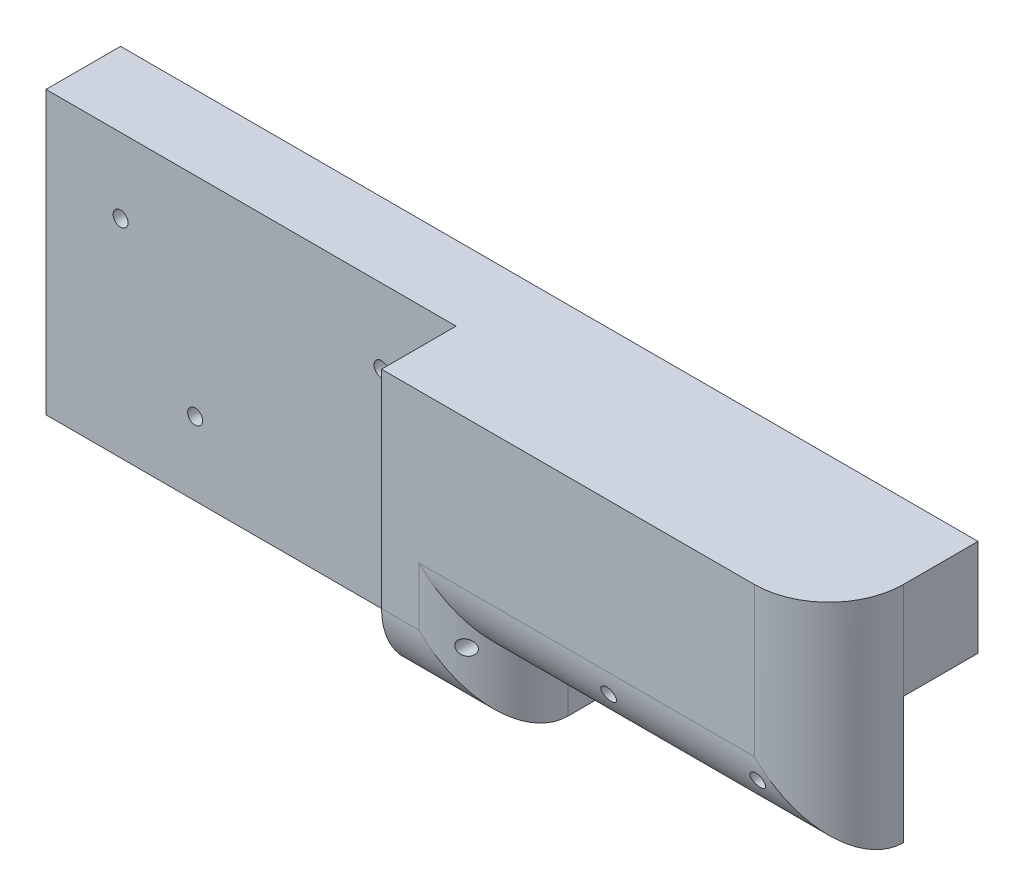
SolidWorks part; units mm, degrees
ref_plane "Plan de face" through (0, 0, 0) normal (0, 0, 1) x (1, 0, 0)
ref_plane "Plan de dessus" through (0, 0, 0) normal (0, 1, 0) x (1, 0, 0)
ref_plane "Plan de droite" through (0, 0, 0) normal (1, 0, 0) x (0, 0, -1)
sketch "Esquisse1" plane through (0, 0, 40) normal (0, 0, 1) x (1, 0, 0)
  line L0 (-121.1414, -130.4642) -> (-181.1414, -130.4642)
  line L1 (-121.1414, -130.4642) -> (-121.1414, -100.4642)
  line L2 (-181.1414, -130.4642) -> (-181.1414, -100.4642)
  line L3 (-121.1414, -100.4642) -> (-181.1414, -100.4642)
  line L6 (-181.1414, -130.4642) -> (-181.1414, -138.2665)
  line L7 (-181.1414, -130.4642) -> (-166.1414, -130.4642)
  line L8 (-181.1414, -138.2665) -> (-166.1414, -138.2665)
  line L9 (-166.1414, -130.4642) -> (-166.1414, -138.2665)
  line L12 (-166.1414, 57.3381) -> (-166.1414, 49.5358) construction
  line L13 (-181.1414, 57.3381) -> (-181.1414, 19.5358) construction
  line M11 (-166.1414, -125.4642) -> (-166.1414, -130.4642)
  line M14 (-121.1414, -113.4642) -> (-161.1414, -113.4642)
  line M15 (-161.1414, -113.4642) -> (-161.1414, -125.4642)
  line M16 (-161.1414, -125.4642) -> (-166.1414, -125.4642)
  dimension "D2" = 30
extrude "Boss.-Extru.1" add sketch "Esquisse1" along normal blind 10 contours L1 L3 L2 L0 M11 M16 M15 M14 | L9 L0 L6 L8 | L0 L1 L3 L2 region at (-173.6414, -134.3653, 40) region at (-157.0661, -111.1423, 40)
sketch "Esquisse2" plane through (0, 0, 40) normal (0, 0, -1) x (-1, 0, 0)
  line L0 (121.1414, -100.4642) -> (121.1414, -113.4642)
  line L1 (121.1414, -100.4642) -> (161.1414, -100.4642)
  line L2 (121.1414, -113.4642) -> (161.1414, -113.4642)
  line L3 (161.1414, -100.4642) -> (161.1414, -113.4642)
  line L4 (121.1414, -130.4642) -> (121.1414, -100.4642) construction
  line L5 (161.1414, -113.4642) -> (121.1414, -113.4642) construction
  line L6 (181.1414, -138.2665) -> (181.1414, -100.4642) construction
  line L7 (161.1414, -100.4642) -> (161.1414, -125.4642)
  line L8 (161.1414, -100.4642) -> (181.1414, -100.4642)
  line L9 (161.1414, -125.4642) -> (181.1414, -125.4642)
  line L10 (181.1414, -100.4642) -> (181.1414, -125.4642)
  line L11 (181.1414, -138.2665) -> (166.1414, -138.2665) construction
  line L12 (166.1414, -138.2665) -> (166.1414, -125.4642)
  line L13 (166.1414, -138.2665) -> (236.1414, -138.2665)
  line L14 (166.1414, -125.4642) -> (236.1414, -125.4642)
  line L15 (236.1414, -138.2665) -> (236.1414, -125.4642)
  line L17 (236.1414, 19.5358) -> (236.1414, 57.3381) construction
  line L18 (181.1414, -125.4642) -> (181.1414, -100.4642)
  line L19 (181.1414, -125.4642) -> (236.1414, -125.4642)
  line L20 (181.1414, -100.4642) -> (236.1414, -100.4642)
  line L21 (236.1414, -125.4642) -> (236.1414, -100.4642)
  point P9 (171.1414, -100.4642)
  point P18 (166.1414, -138.2665)
  line M7 (166.1414, -130.4642) -> (166.1414, -138.2665)
  line M8 (166.1414, -138.2665) -> (181.1414, -138.2665)
  line M9 (181.1414, -138.2665) -> (181.1414, -100.4642)
  line M10 (181.1414, -100.4642) -> (121.1414, -100.4642)
  line M11 (121.1414, -100.4642) -> (121.1414, -130.4642)
extrude "Boss.-Extru.2" add sketch "Esquisse2" along normal blind 10 contours L13 L15 L14 M9 | L12 L9 M7 M8 M9 | L7 L9 L3 M9 M10 | L3 L2 M10 M11 | L18 L19 L21 L20 region at (-141.1414, -106.9642, 40) region at (-171.1414, -112.9642, 40) region at (-173.6414, -131.8653, 40) region at (-208.6414, -131.8653, 40)
sketch "Esquisse3" plane through (0, 0, 30) normal (0, 0, -1) x (-1, 0, 0)
  line L0 (166.1414, -138.2665) -> (166.1414, -125.4642)
  line L1 (166.1414, -138.2665) -> (226.1414, -138.2665)
  line L2 (166.1414, -125.4642) -> (226.1414, -125.4642)
  line L3 (226.1414, -138.2665) -> (226.1414, -125.4642)
  line L4 (226.1414, -125.4642) -> (226.1414, -140.4642) construction
  line L5 (166.1414, -138.2665) -> (166.1414, -125.4642) construction
  line L6 (161.1414, -125.4642) -> (166.1414, -125.4642) construction
  point P8 (166.1414, -138.2665)
  point P10 (166.1414, -125.2461)
  point P11 (166.1414, -125.4642)
extrude "Boss.-Extru.3" add sketch "Esquisse3" along normal blind 10
sketch "Esquisse4" plane through (0, 0, 50) normal (0, 0, 1) x (1, 0, 0)
  line L1 (-236.1414, -100.4642) -> (-181.1414, -100.4642) construction
  line L2 (-236.1414, -138.2665) -> (-236.1414, -100.4642) construction
  line L3 (-181.1414, -138.2665) -> (-181.1414, -100.4642) construction
  circle A0 centre (-151.1414, -123.4642) radius 1
  circle A1 centre (-131.1414, -123.4642) radius 1
  circle A2 centre (-171.1414, -128.4642) radius 1
  circle A3 centre (-216.1414, -128.4642) radius 1
  circle A4 centre (-226.1414, -110.4642) radius 1
  circle A5 centre (-191.1414, -110.4642) radius 1
  circle A6 centre (-151.1414, -123.4642) radius 1 construction
  circle A7 centre (-131.1414, -123.4642) radius 1 construction
  circle A10 centre (-216.1414, -128.4642) radius 1 construction
  circle A11 centre (-171.1414, -128.4642) radius 1 construction
  dimension "D1" = 10
  dimension "D2" = 10
  dimension "D3" = 10
  dimension "D4" = 10
  dimension "D5" = 2
  dimension "D6" = 2
fillet "Congé1" radius 10 4 edges at (-121.1414, -115.4642, 50) (-173.6414, -138.2665, 50) (-166.1414, -134.3653, 50) (-143.6414, -130.4642, 50)
extrude "Enlèv. mat.-Extru.1" cut sketch "Esquisse4" against normal through all
